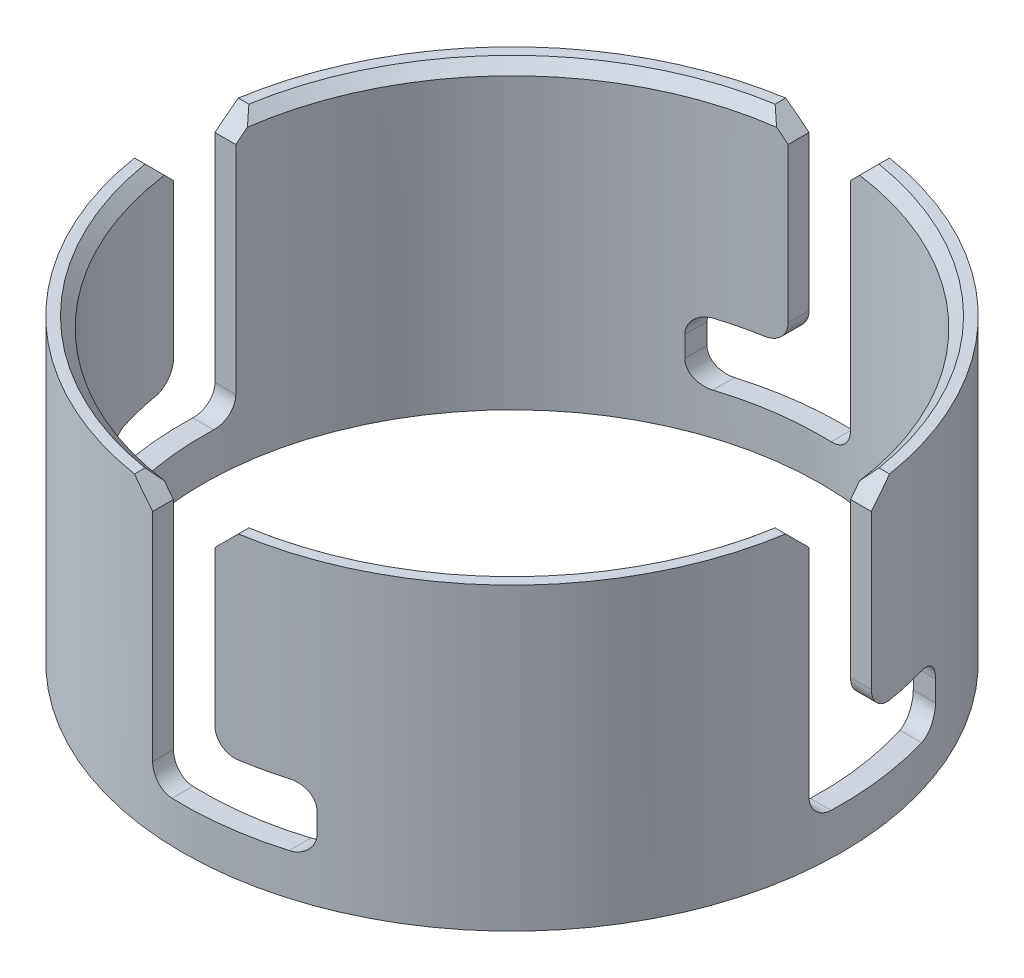
SolidWorks part; units mm, degrees
material "Plain Carbon Steel"
ref_plane "Front Plane" through (0, 0, 0) normal (0, 0, 1) x (1, 0, 0)
ref_plane "Top Plane" through (0, 0, 0) normal (0, 1, 0) x (1, 0, 0)
ref_plane "Right Plane" through (0, 0, 0) normal (1, 0, 0) x (0, 0, -1)
sketch "Sketch2" plane through (0, 0, 0) normal (1, 0, 0) x (0, 0, -1)
  line L0 (-74.375, 0) -> (-79.375, 0)
  line L1 (-79.375, 0) -> (-79.375, 72.15)
  line L2 (-79.375, 72.15) -> (-74.375, 72.15)
  line L5 (-74.375, 72.15) -> (-74.375, 0)
  dimension "D1" = 79.375
  dimension "D2" = 72.15
  dimension "D3" = 5
ref_axis "Axis1" through (0, -3.6075, 0) along (0, 1, 0)
revolve "Revolve1" add sketch "Sketch2" angle 360 about axis through (0, -3.6075, 0) along (0, 1, 0)
sketch "Sketch3" plane through (0, 0, 0) normal (1, 0, 0) x (0, 0, -1)
  line L0 (-7.5, 72.15) -> (7.5, 72.15)
  line L1 (79.375, 72.15) -> (-79.375, 72.15) construction
  line L2 (7.5, 72.15) -> (7.5, 10)
  line L3 (7.5, 10) -> (-27.5, 10)
  line L4 (-27.5, 10) -> (-27.5, 25)
  line L5 (-27.5, 25) -> (-7.5, 25)
  line L6 (-7.5, 25) -> (-7.5, 72.15)
  line L7 (0, -3.6075) -> (0, 75.7575) construction
  line L8 (0, 0) -> (0, 47.5309) construction
  line L9 (-79.375, 0) -> (79.375, 0) construction
  dimension "D1" = 10
  dimension "D2" = 15
  dimension "D3" = 15
  dimension "D4" = 20
extrude "Cut-Extrude1" cut sketch "Sketch3" against normal through all
fillet "Fillet1" radius 5 2 edges at (-76.5079, 25, 7.5) (-76.5079, 10, -7.5)
chamfer "Chamfer1" distance 5 angle 45 2 edges at (-76.5079, 72.15, 7.5) (-76.5079, 72.15, -7.5)
fillet "Fillet3" radius 5 2 edges at (-71.7816, 25, 27.5) (-71.7816, 10, 27.5)
pattern_circular "CirPattern1" count 4 over 360 about axis through (0, -3.6075, 0) along (0, 1, 0) of "Fillet3", "Chamfer1", "Fillet1", "Cut-Extrude1"
chamfer "Chamfer2" distance 2.5 angle 45 4 edges at (-52.5911, 72.15, -52.5911) (52.5911, 72.15, -52.5911) (52.5911, 72.15, 52.5911) (-52.5911, 72.15, 52.5911)
equation "\"TubeDiameter\" = 6.250in"
equation "\"D1@Sketch2\"=\"TubeDiameter\"/2"
